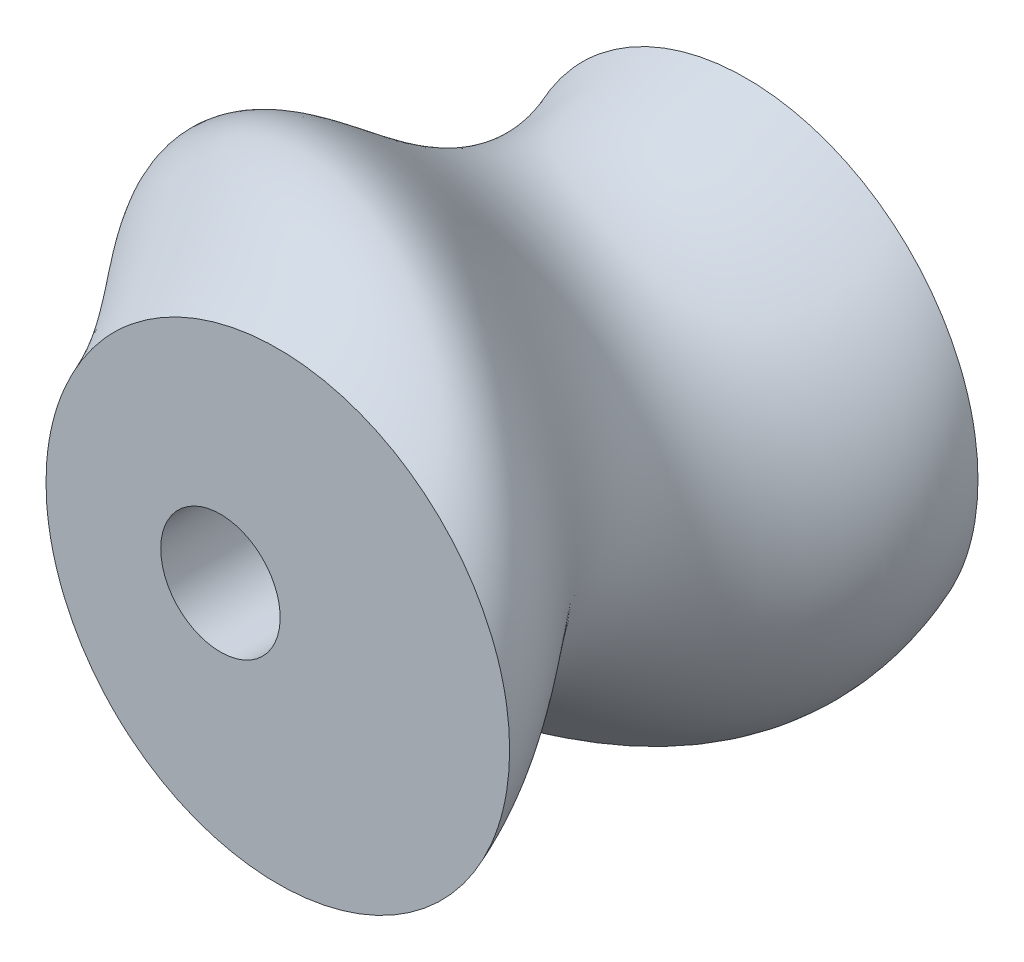
SolidWorks part; units mm, degrees
ref_plane "Ebene vorne" through (0, 0, 0) normal (0, 0, 1) x (1, 0, 0)
ref_plane "Ebene oben" through (0, 0, 0) normal (0, 1, 0) x (1, 0, 0)
ref_plane "Ebene rechts" through (0, 0, 0) normal (1, 0, 0) x (0, 0, -1)
sketch "Skizze2" plane through (0, 0, 0) normal (0, 0, 1) x (1, 0, 0)
  circle A0 centre (0, 0) radius 9.8996
  dimension "D1" = 19.7991
ref_plane "Ebene1" through (0, 0, 0) normal (0, 0, 1) x (1, 0, 0)
sketch "Skizze3" plane through (0, 0, 0) normal (0, 0, 1) x (1, 0, 0)
  circle A0 centre (-2.45, 0) radius 2.55
  point P0 (-2.45, 0)
  dimension "D2" = 5.1
  dimension "D1" = 2.45
curve "Spirale/Helix1" pitch 20 height 20 radius 2.55 left hand yes centre (-2.45, 0, 0) axis (0, 0, 1) start towards (1, 0, 0)
sweep "Austragung1" add profiles "Skizze2" path "Spirale/Helix1"
sketch "Skizze5" plane through (0, 0, 20) normal (0, 0, 1) x (1, 0, 0)
  circle A0 centre (0, 0) radius 2.5
  dimension "D1" = 5
ref_plane "Ebene3" through (0.1, 0, 0) normal (0, -0.6252, 0.7804) x (1, 0, 0)
extrude "Schnitt-Linear austragen2" cut sketch "Skizze3<2>" along normal blind 27
sketch "Skizze3<2>" plane through (0, 0, 0) normal (0, 0, 1) x (1, 0, 0) same geometry as "Skizze3"
ref_axis "Achse2" through (-2.45, 0, 72.3086) along (0, 0, -1)
